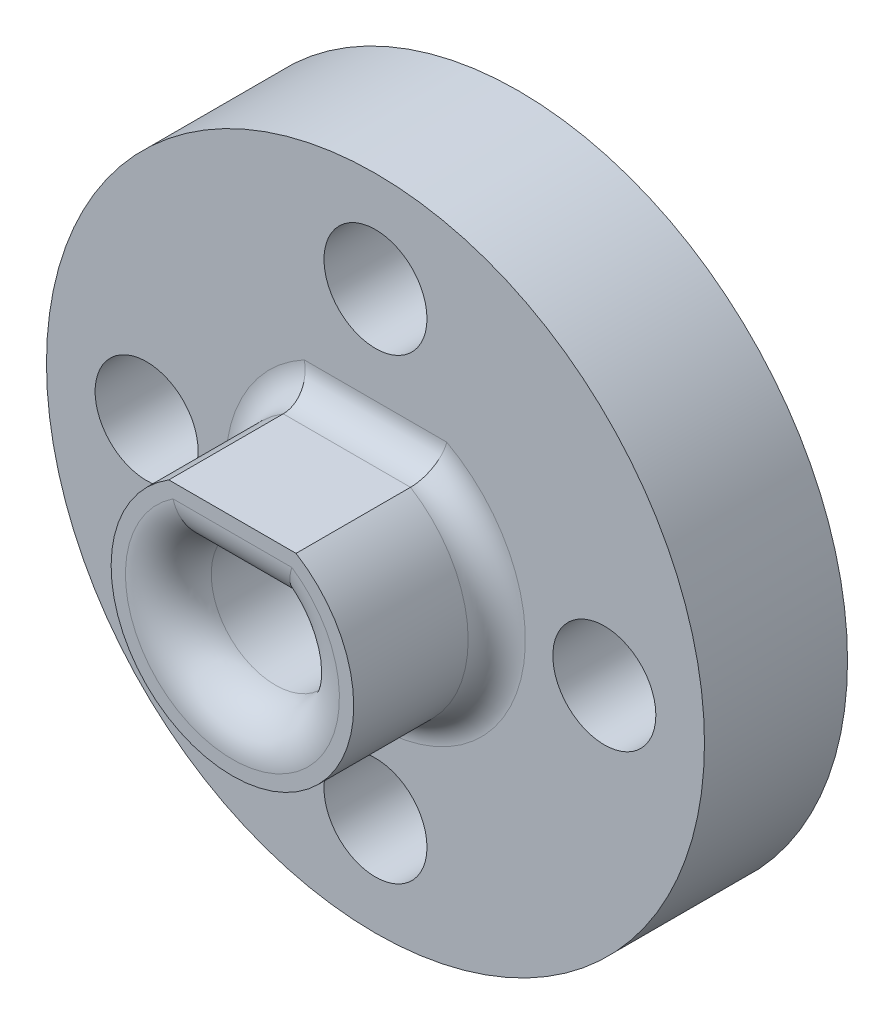
SolidWorks part; units mm, degrees
ref_plane "Front Plane" through (0, 0, 0) normal (0, 0, 1) x (1, 0, 0)
ref_plane "Top Plane" through (0, 0, 0) normal (0, 1, 0) x (1, 0, 0)
ref_plane "Right Plane" through (0, 0, 0) normal (1, 0, 0) x (0, 0, -1)
sketch "Sketch1" plane through (0, 0, 0) normal (0, 0, 1) x (1, 0, 0)
  line L0 (1.5574, 1.61) -> (-1.5574, 1.61)
  circle A0 centre (0, 8) radius 1.8
  circle A1 centre (8, 0) radius 1.8
  circle A2 centre (0, -8) radius 1.8
  circle A3 centre (-8, 0) radius 1.8
  circle A4 centre (0, 0) radius 11.5
  arc A5 (1.5574, 1.61) -> (-1.5574, 1.61) centre (0, 0) cw
  point P0 (0, 0)
  point P13 (0, 0)
  point P17 (0, -2.24)
  dimension "D1" = 3.6
  dimension "D4" = 23
  dimension "D5" = 2.24
  dimension "D2" = 8
  dimension "D6" = 3.85
  dimension "D3" = 4
extrude "Boss-Extrude1" add sketch "Sketch1" along normal blind 5 contours A4 A0 A1 A2 A3 L0 A5 region at (-11.1747, 0, 0)
extrude "Extrude-Thin1" add sketch "Sketch1<4>" along normal blind 5 from surface thin contours L0 A5 starting at face at (1.8, 8, 5) thin type one direction wall 2
sketch "Sketch1<4>" plane through (0, 0, 0) normal (0, 0, 1) x (1, 0, 0) same geometry as "Sketch1"
fillet "Fillet1" radius 1 2 edges at (0, -4.24, 5) (0, 3.61, 5)
fillet "Fillet2" radius 1.5 2 edges at (0, 1.61, 10) (0, -2.24, 10)
